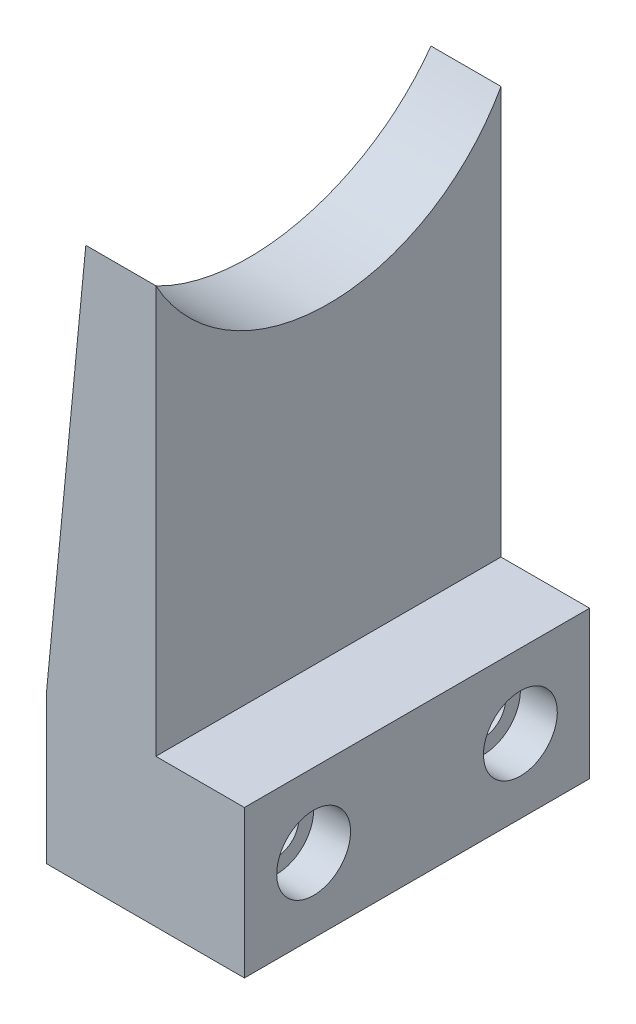
SolidWorks part; units mm, degrees
ref_plane "Front Plane" through (0, 0, 0) normal (0, 0, 1) x (1, 0, 0)
ref_plane "Top Plane" through (0, 0, 0) normal (0, 1, 0) x (1, 0, 0)
ref_plane "Right Plane" through (0, 0, 0) normal (1, 0, 0) x (0, 0, -1)
sketch "Gripper Attachment Base Sketch" plane through (0, 0, 0) normal (0, 0, 1) x (1, 0, 0)
  line L5 (5.5563, 7.5) -> (-5.5562, 7.5)
  line L6 (5.5563, 7.5) -> (5.5563, -7.5)
  line L7 (5.5563, -7.5) -> (-5.5562, -7.5)
  line L8 (-5.5562, 7.5) -> (-5.5562, -7.5)
  line L9 (5.5563, 7.5) -> (-5.5562, -7.5) construction
  line L10 (5.5563, -7.5) -> (-5.5562, 7.5) construction
  point P0 (0, 0)
  dimension "D1" = 11.1125
  dimension "D2" = 15
extrude "Gripper Attachment Base" add sketch "Gripper Attachment Base Sketch" along normal blind 35.0589 contours L7 L8 L5 L6
sketch "Through-Holes Sketch" plane through (5.5563, 0, 0) normal (1, 0, 0) x (0, 0, -1)
  line L1 (-35.0589, 7.5) -> (0, 7.5) construction
  circle A0 centre (-28.0294, 0) radius 2.25
  circle A1 centre (-7.0294, 0) radius 2.25
  point P5 (-17.5294, 7.5)
  dimension "D1" = 4.5
  dimension "D2" = 4.5
  dimension "D3" = 21
  dimension "D4" = 10.5
  dimension "D5" = 7.5
extrude "Screw Through-Holes" cut sketch "Through-Holes Sketch" against normal through all
sketch "Socket Recesses Sketch" plane through (5.5563, 0, 0) normal (1, 0, 0) x (0, 0, -1)
  circle A0 centre (-28.0294, 0) radius 3.75
  circle A1 centre (-7.0294, 0) radius 3.75
  circle A2 centre (-28.0294, 0) radius 2.25 construction
  circle A3 centre (-7.0294, 0) radius 2.25 construction
  dimension "D1" = 7.5
  dimension "D2" = 7.5
extrude "Socket Recesses" cut sketch "Socket Recesses Sketch" against normal blind 3.75
sketch "Finger Cavity Sketch" plane through (-5.5562, 0, 0) normal (-1, 0, 0) x (0, 0, 1)
  line L0 (2.5294, 7.5) -> (2.5294, -7.5)
  line L1 (0, 7.5) -> (35.0589, 7.5)
  line L2 (0, 7.5) -> (0, -7.5)
  line L3 (0, -7.5) -> (35.0589, -7.5)
  line L4 (35.0589, 7.5) -> (35.0589, -7.5)
  line L9 (32.5294, 7.5) -> (32.5294, -7.5)
  line M13 (0, 7.5) -> (0, -7.5)
  line M14 (0, -7.5) -> (35.0589, -7.5)
  line M15 (35.0589, -7.5) -> (35.0589, 7.5)
  line M16 (35.0589, 7.5) -> (0, 7.5)
  dimension "D1" = 30
  dimension "D2" = 2.5294
extrude "Finger Cavity" add sketch "Finger Cavity Sketch" along normal blind 9 contours L0 M16 M13 M14 | L9 L3 M16 M15 region at (-5.5562, 0, 1.2647) region at (-5.5562, 0, 33.7941)
ref_plane "Electronics Plate Plane" through (-3.4437, 0, 0) normal (1, 0, 0) x (0, 0, -1)
sketch "Thickener Base Sketch" plane through (-3.4437, 0, 0) normal (1, 0, 0) x (0, 0, -1)
  line L0 (-35.0589, -7.5) -> (-35.0589, 7.5) construction
  line L6 (0, 7.5) -> (-35.0589, 7.5)
  line L7 (0, 7.5) -> (0, 48.8959)
  line L9 (-35.0589, 7.5) -> (-35.0589, 48.8959)
  arc A1 (-35.0589, 48.8959) -> (0, 48.8959) centre (-17.5294, 58.525) ccw
  dimension "D3" = 41.3959
  dimension "D4" = 20
extrude "Thickener Base" add sketch "Thickener Base Sketch" against normal up to surface (11.1125 mm away) up to face at (-14.5563, 0, 1.2647)
sketch "Define Thickness Plane 1" plane through (0, 0, 35.0589) normal (0, 0, 1) x (1, 0, 0)
  line L0 (-14.5563, 7.5) -> (-10.5563, 48.8959) construction
  line L1 (-14.5563, -7.5) -> (-14.5563, 48.8959) construction
  line L2 (-14.5563, 48.8959) -> (-3.4438, 48.8959) construction
  dimension "D1" = 4
sketch "Derfine Thickness Plane 2" plane through (0, 0, 0) normal (0, 0, -1) x (-1, 0, 0)
  line L0 (14.5563, 7.5) -> (10.5563, 48.8959) construction
  line L1 (14.5563, 48.8959) -> (14.5563, -7.5) construction
  line L2 (14.5563, 48.8959) -> (3.4438, 48.8959) construction
  dimension "D1" = 4
ref_plane "Thickness Plane" through (-15.1396, 1.4629, 0) normal (0.9954, -0.0962, 0) x (0, 0, -1)
sketch "Thickness Cutoff Sketch" plane through (-15.1396, 1.4629, 0) normal (0.9954, -0.0962, 0) x (0, 0, -1)
  line L0 (0, 47.2692) -> (0, -8.8652) construction
  line L1 (-45.0589, -17.9996) -> (10, -17.9996)
  line L2 (-45.0589, -17.9996) -> (-45.0589, 57.2692)
  line L3 (-45.0589, 57.2692) -> (10, 57.2692)
  line L4 (10, -17.9996) -> (10, 57.2692)
  line L5 (-35.0589, -8.8652) -> (-35.0589, 47.2692) construction
  line L6 (-32.5294, -7.9996) -> (-2.5294, -7.9996) construction
  dimension "D1" = 10
  dimension "D2" = 10
  dimension "D3" = 10
  dimension "D4" = 10
extrude "Thickness Cutoff" cut sketch "Thickness Cutoff Sketch" against normal through all
